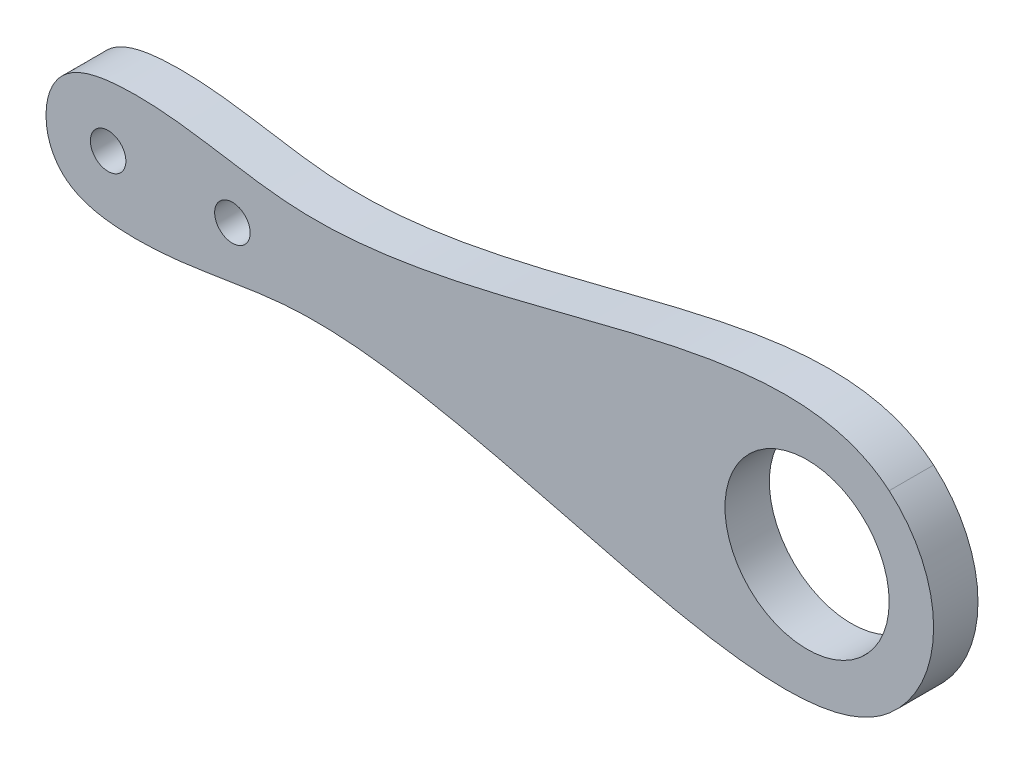
SolidWorks part; units mm, degrees
ref_plane "Front Plane" through (0, 0, 0) normal (1, 0, 0) x (0, 1, 0)
ref_plane "Top Plane" through (0, 0, 0) normal (0, 0, 1) x (0, 1, 0)
ref_plane "Right Plane" through (0, 0, 0) normal (0, 1, 0) x (-1, 0, 0)
sketch "Sketch1" plane through (0, 0, 0) normal (0, 0, 1) x (-1, 0, 0)
  line L0 (0, 0) -> (10.015, 0)
  line L16 (144, 10) -> (144, 0) construction
  line L17 (200, 0) -> (190, 0)
  line L18 (200, 0) -> (200, 10) construction
  line L19 (188.4209, 10) -> (129.4316, 10) construction
  line L21 (162, 0) -> (182, 0)
  line L24 (47.015, 0) -> (154, 0)
  arc A10 (47.015, 0) -> (10.015, 0) centre (28.515, 0) ccw
  arc A11 (154, 0) -> (162, 0) centre (158, 0) cw
  arc A12 (182, 0) -> (190, 0) centre (186, 0) cw
  circle A13 centre (186, 0) radius 14 construction
  arc A14 (10.015, 21.6991) -> (0, 0) centre (28.515, 0) ccw
  spline S0 degree 3 poles (10.015, 21.6991) (35.6182, 43.5277) (116.1003, -2.6809) (172.9675, 15.9282) (196.3224, 12.4161) (200, 4.1781) (200, 0) knots 0 0 0 0 0.679549 0.872609 0.945194 1 1 1 1
  point P2 (0, 0)
  point P5 (94.9315, 14)
  point P16 (64.9711, 10)
  point P18 (58.4384, 19.0572)
  point P24 (126.4688, 10)
  point P26 (59.5647, 16.354)
  point P27 (114.0791, 16.1287)
  point P30 (61.1416, 16.354)
  point P31 (100.5632, 47.8913)
  point P32 (0, 0)
  point P33 (65.1963, 21.6991)
  point P34 (67.2237, 10)
  point P35 (0, 0)
  point P36 (0, 0)
  dimension "D4" = 4
  dimension "D5" = 4
  dimension "D3" = 200
  dimension "D7" = 10
  dimension "D8" = 20
  dimension "D6" = 10
  dimension "D9" = 10
  dimension "D10" = 4
  dimension "D11" = 10.015
  dimension "D2" = 37
extrude "Boss-Extrude1" add sketch "Sketch1" along normal blind 10
mirror "Mirror1" about plane through (-47.015, 0, 10) normal (0, -1, 0) of "Boss-Extrude1"
equation "\"SHIN_LENGTH\"=200"
equation "\"KNEE_JOINT_DIAMETER\"=30"
equation "\"FOOT_JOINT_DIAMETER\"= 50"
equation "\"MOTOR_DIAMETER\"=37"
equation "\"JOINT_BORE_DIAMETER\"=10"
equation "\"D3@Sketch1\"=\"SHIN_LENGTH\""
equation "\"BearingBore\"=4"
equation "\"D4@Sketch1\"=\"BearingBore\""
equation "\"D5@Sketch1\"=\"BearingBore\""
equation "\"MinShinWidth\"= 20"
equation "\"D9@Sketch1\"=\"MinShinWidth\"/2"
equation "\"D2@Sketch1\"=\"MOTOR_DIAMETER\""
equation "\"ShinThickness\"=10"
equation "\"D1@Boss-Extrude1\"=\"ShinThickness\""
equation "\"KneeLength\"=20"
equation "\"D8@Sketch1\"=\"KneeLength\""
